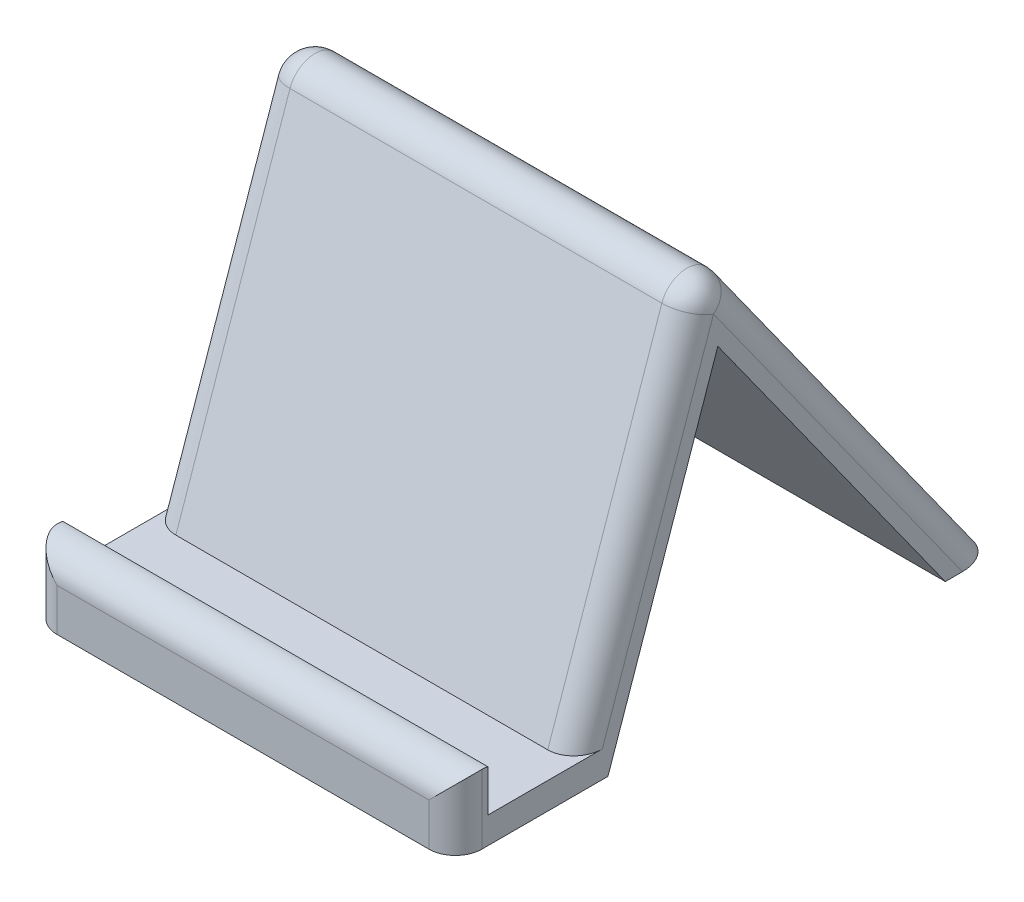
SolidWorks part; units mm, degrees
ref_plane "Front Plane" through (0, 0, 0) normal (0, 0, 1) x (1, 0, 0)
ref_plane "Top Plane" through (0, 0, 0) normal (0, 1, 0) x (1, 0, 0)
ref_plane "Right Plane" through (0, 0, 0) normal (1, 0, 0) x (0, 0, -1)
sketch "Base" plane through (0, 0, 0) normal (0, 1, 0) x (1, 0, 0)
  line L1 (-40, 50.8) -> (40, 50.8)
  line L2 (-40, 50.8) -> (-40, -50.8)
  line L3 (-40, -50.8) -> (40, -50.8)
  line L4 (40, 50.8) -> (40, -50.8)
  line L5 (-40, 50.8) -> (40, -50.8) construction
  line L6 (-40, -50.8) -> (40, 50.8) construction
  point P0 (0, 0)
  dimension "D1" = 80
  dimension "D2" = 101.6
extrude "Boss-Extrude1" add sketch "Base" along normal blind 76.2
sketch "Sketch2" plane through (-40, 0, 0) normal (-1, 0, 0) x (0, 0, 1)
  line L0 (-50.8, 0) -> (3.7832, 76.2)
  line L1 (50.8, 76.2) -> (50.8, 0) construction
  line L2 (3.7832, 76.2) -> (27.7228, 7.0148)
  line L4 (27.7228, 7.0148) -> (50.8, 15)
  line L5 (50.8, 15) -> (50.8, 0)
  line L11 (-50.8, 76.2) -> (50.8, 76.2) construction
  line L12 (-50.8, 0) -> (50.8, 0)
  dimension "D1" = 15
extrude "Cut-Extrude1" cut sketch "Sketch2" against normal through all flip side to cut
sketch "Sketch3" plane through (-40, 0, 0) normal (-1, 0, 0) x (0, 0, 1)
  line L0 (-41.4268, 0) -> (22.0868, 0)
  line L2 (-41.4268, 0) -> (1.3993, 59.7866)
  line L3 (-50.8, 0) -> (50.8, 0) construction
  line L6 (22.0868, 0) -> (1.3993, 59.7866)
  line L7 (27.7228, 7.0148) -> (3.7832, 76.2) construction
  line L8 (3.7832, 76.2) -> (-50.8, 0) construction
  dimension "D2" = 7.62
  dimension "D3" = 7.62
  dimension "D4" = 7.62
  dimension "D5" = 7.62
extrude "Cut-Extrude2" cut sketch "Sketch3" against normal through all
sketch "Sketch4" plane through (-40, 0, 0) normal (-1, 0, 0) x (0, 0, 1)
  line L0 (27.7228, 7.0148) -> (28.42, 5)
  line L1 (28.42, 5) -> (44.6904, 5)
  line L2 (22.0868, 0) -> (50.8, 0) construction
  line L3 (50.8, 15) -> (27.7228, 7.0148) construction
  line L4 (27.7228, 7.0148) -> (3.7832, 76.2) construction
  line L7 (44.6904, 12.886) -> (44.6904, 5)
  dimension "D1" = 5
  dimension "D2" = 180
extrude "Cut-Extrude5" cut sketch "Sketch4" against normal through all and the other way through all flip side to cut
fillet "Fillet9" radius 5 8 edges at (40, 40.6, 16.1016) (40, 7.5, 50.8) (0, 15, 50.8) (-40, 7.5, 50.8) (-40, 40.6, 16.1016) (-40, 38.1, -23.5084) (40, 38.1, -23.5084) (0, 76.2, 3.7832)
